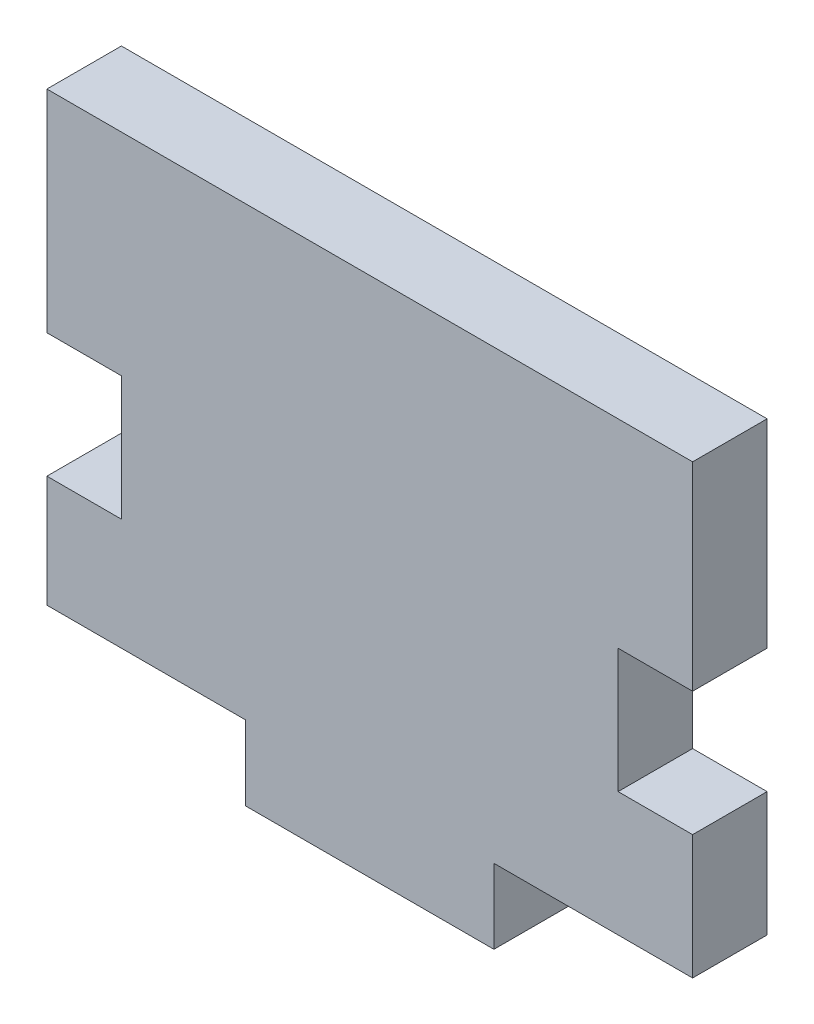
SolidWorks part; units mm, degrees
ref_plane "Front Plane" through (0, 0, 0) normal (0, 0, 1) x (1, 0, 0)
ref_plane "Top Plane" through (0, 0, 0) normal (0, 1, 0) x (1, 0, 0)
ref_plane "Right Plane" through (0, 0, 0) normal (1, 0, 0) x (0, 0, -1)
sketch "Sketch1" plane through (0, 0, 0) normal (0, 0, 1) x (1, 0, 0)
  line L0 (0, 0) -> (0, 21) construction
  line L1 (-26, 21) -> (26, 21)
  line L2 (-26, 21) -> (-26, -21)
  line L3 (-26, -21) -> (26, -21)
  line L4 (26, 21) -> (26, -21)
  line L5 (0, 0) -> (26, 0) construction
  dimension "D1" = 52
  dimension "D2" = 42
extrude "Boss-Extrude1" add sketch "Sketch1" along normal blind 6
sketch "Sketch2" plane through (0, 0, 6) normal (0, 0, 1) x (1, 0, 0)
  line L0 (-26, 21) -> (-26, -21) construction
  line L1 (-26, -15) -> (-10, -15)
  line L2 (-26, -15) -> (-26, -21)
  line L3 (-26, -21) -> (-10, -21)
  line L4 (-10, -15) -> (-10, -21)
  line L5 (-26, -21) -> (26, -21) construction
  line L6 (0, 21) -> (0, -21) construction
  line L7 (10, -15) -> (26, -15)
  line L8 (10, -15) -> (10, -21)
  line L9 (10, -21) -> (26, -21)
  line L10 (26, -15) -> (26, -21)
  line L11 (26, 21) -> (-26, 21) construction
  dimension "D1" = 20
  dimension "D2" = 6
extrude "Cut-Extrude1" cut sketch "Sketch2" against normal through all
sketch "Sketch3" plane through (0, 0, 0) normal (0, 0, -1) x (-1, 0, 0)
  line L0 (-26, -15) -> (-26, 21) construction
  line L1 (-20, 5) -> (-26, 5)
  line L2 (-20, 5) -> (-20, -5)
  line L3 (-20, -5) -> (-26, -5)
  line L4 (-26, 5) -> (-26, -5)
  line L5 (-26, -5) -> (-20, -5) construction
  line L6 (26, 21) -> (26, -15) construction
  line L7 (20, 4) -> (26, 4)
  line L8 (20, 4) -> (20, -6)
  line L9 (20, -6) -> (26, -6)
  line L10 (26, 4) -> (26, -6)
  line L11 (20, -6) -> (26, -6) construction
extrude "Cut-Extrude2" cut sketch "Sketch3" against normal through all
